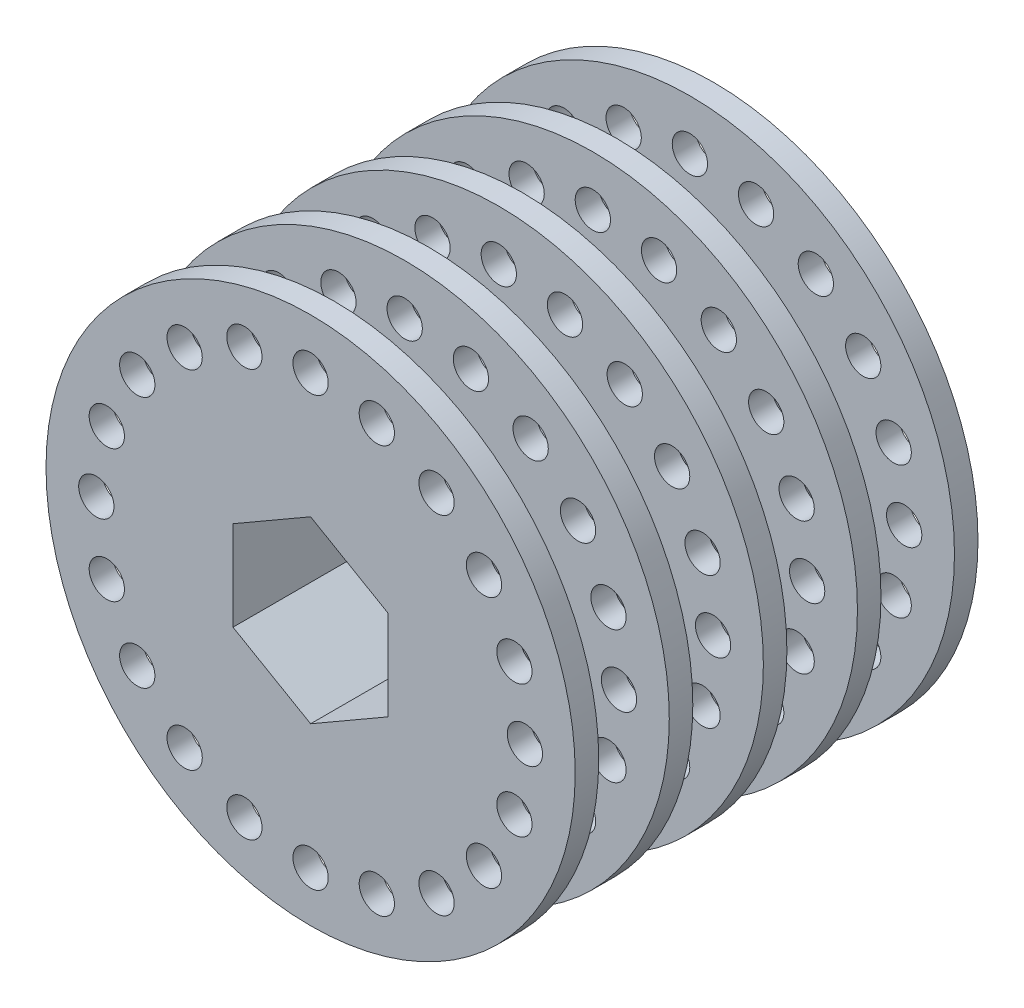
SolidWorks part; units mm, degrees
ref_plane "Front Plane" through (0, 0, 0) normal (0, 0, 1) x (1, 0, 0)
ref_plane "Top Plane" through (0, 0, 0) normal (0, 1, 0) x (1, 0, 0)
ref_plane "Right Plane" through (0, 0, 0) normal (1, 0, 0) x (0, 0, -1)
sketch "Sketch1" plane through (0, 0, 0) normal (0, 0, 1) x (1, 0, 0)
  circle A0 centre (0, 0) radius 10.16
  circle A1 centre (0, 0) radius 22.5
  circle A2 centre (0, 18.2218) radius 1.5
  circle A3 centre (5.6309, 17.33) radius 1.5
  circle A4 centre (10.7105, 14.7418) radius 1.5
  circle A5 centre (14.7418, 10.7105) radius 1.5
  circle A6 centre (17.33, 5.6309) radius 1.5
  circle A7 centre (18.2218, 0) radius 1.5
  circle A8 centre (17.33, -5.6309) radius 1.5
  circle A9 centre (14.7418, -10.7105) radius 1.5
  circle A10 centre (10.7105, -14.7418) radius 1.5
  circle A11 centre (5.6309, -17.33) radius 1.5
  circle A12 centre (0, -18.2218) radius 1.5
  circle A13 centre (-5.6309, -17.33) radius 1.5
  circle A14 centre (-10.7105, -14.7418) radius 1.5
  circle A15 centre (-14.7418, -10.7105) radius 1.5
  circle A16 centre (-17.33, -5.6309) radius 1.5
  circle A17 centre (-18.2218, 0) radius 1.5
  circle A18 centre (-17.33, 5.6309) radius 1.5
  circle A19 centre (-14.7418, 10.7105) radius 1.5
  circle A20 centre (-10.7105, 14.7418) radius 1.5
  circle A21 centre (-5.6309, 17.33) radius 1.5
  point P47 (0, 0)
  dimension "D1" = 20.32
  dimension "D2" = 45
  dimension "D3" = 3
  dimension "D4" = 20
extrude "Boss-Extrude1" add sketch "Sketch1" along normal blind 2 contours A0 | A1 A21 A20 A19 A18 A17 A16 A15 A14 A13 A12 A11 A10 A9 A8 A7 A6 A5 A4 A3 A2 A0 region at (0, 0, 0) region at (-21.8636, 0, 0)
extrude "Boss-Extrude2" add sketch "Sketch1<3>" against normal blind 6.25 contours A0 region at (0, 0, 0)
sketch "Sketch1<3>" plane through (0, 0, 0) normal (0, 0, 1) x (1, 0, 0) same geometry as "Sketch1"
pattern_linear "LPattern2" count 4 spacing 8 along (0, 0, -1) of "Boss-Extrude2", "Boss-Extrude1"
sketch "Sketch2" plane through (0, 0, -30.25) normal (0, 0, -1) x (-1, 0, 0)
  circle A1 centre (0, 0) radius 10.16 construction
  circle A2 centre (0, 0) radius 22.5 construction
  circle A3 centre (0, 0) radius 10.16
  circle A4 centre (0, 0) radius 22.5
  circle A5 centre (10.7105, 14.7418) radius 1.5
  circle A6 centre (10.7105, 14.7418) radius 1.5
  circle A7 centre (14.7418, 10.7105) radius 1.5
  circle A8 centre (14.7418, 10.7105) radius 1.5
  circle A9 centre (17.33, 5.6309) radius 1.5
  circle A10 centre (17.33, 5.6309) radius 1.5
  circle A11 centre (18.2218, 0) radius 1.5
  circle A12 centre (18.2218, 0) radius 1.5
  circle A13 centre (17.33, -5.6309) radius 1.5
  circle A14 centre (17.33, -5.6309) radius 1.5
  circle A15 centre (14.7418, -10.7105) radius 1.5
  circle A16 centre (14.7418, -10.7105) radius 1.5
  circle A17 centre (10.7105, -14.7418) radius 1.5
  circle A18 centre (10.7105, -14.7418) radius 1.5
  circle A19 centre (5.6309, -17.33) radius 1.5
  circle A20 centre (5.6309, -17.33) radius 1.5
  circle A21 centre (0, -18.2218) radius 1.5
  circle A22 centre (0, -18.2218) radius 1.5
  circle A23 centre (-5.6309, -17.33) radius 1.5
  circle A24 centre (-5.6309, -17.33) radius 1.5
  circle A25 centre (-10.7105, -14.7418) radius 1.5
  circle A26 centre (-10.7105, -14.7418) radius 1.5
  circle A27 centre (-14.7418, -10.7105) radius 1.5
  circle A28 centre (-14.7418, -10.7105) radius 1.5
  circle A29 centre (-17.33, -5.6309) radius 1.5
  circle A30 centre (-17.33, -5.6309) radius 1.5
  circle A31 centre (-18.2218, 0) radius 1.5
  circle A32 centre (-18.2218, 0) radius 1.5
  circle A33 centre (-17.33, 5.6309) radius 1.5
  circle A34 centre (-17.33, 5.6309) radius 1.5
  circle A35 centre (-14.7418, 10.7105) radius 1.5
  circle A36 centre (-14.7418, 10.7105) radius 1.5
  circle A37 centre (-10.7105, 14.7418) radius 1.5
  circle A38 centre (-10.7105, 14.7418) radius 1.5
  circle A39 centre (-5.6309, 17.33) radius 1.5
  circle A40 centre (-5.6309, 17.33) radius 1.5
  circle A41 centre (0, 18.2218) radius 1.5
  circle A42 centre (0, 18.2218) radius 1.5
  circle A43 centre (0, 0) radius 10.16
  circle A44 centre (0, 0) radius 10.16
  circle A45 centre (5.6309, 17.33) radius 1.5
  circle A46 centre (5.6309, 17.33) radius 1.5
  circle M22 centre (0, 0) radius 10.16
  dimension "D1" = 0
  dimension "D2" = 0
  dimension "D3" = 0
  dimension "D4" = 0
  dimension "D5" = 0
  dimension "D6" = 0
  dimension "D7" = 0
  dimension "D8" = 0
  dimension "D9" = 0
  dimension "D10" = 0
  dimension "D11" = 0
  dimension "D12" = 0
  dimension "D13" = 0
  dimension "D14" = 0
  dimension "D15" = 0
  dimension "D16" = 0
  dimension "D17" = 0
  dimension "D18" = 0
  dimension "D19" = 0
  dimension "D20" = 0
  dimension "D21" = 0
extrude "Boss-Extrude3" add sketch "Sketch2" along normal blind 2 contours A4 A46 A42 A40 A38 A36 A34 A32 A30 A28 A26 A24 A22 A20 A18 A16 A14 A12 A10 A8 A6 M22 | M22 region at (0, 0, -30.25) region at (21.8636, 0, -30.25)
sketch "Sketch3" plane through (0, 0, -32.25) normal (0, 0, -1) x (-1, 0, 0)
  line L1 (0, 7.621) -> (-6.6, 3.8105)
  line L2 (-6.6, 3.8105) -> (-6.6, -3.8105)
  line L3 (-6.6, -3.8105) -> (0, -7.621)
  line L4 (0, -7.621) -> (6.6, -3.8105)
  line L5 (6.6, -3.8105) -> (6.6, 3.8105)
  line L6 (6.6, 3.8105) -> (0, 7.621)
  circle A0 centre (0, 0) radius 6.6 construction
  circle A2 centre (0, 0) radius 19.05
  dimension "D2" = 38.1
extrude "Cut-Extrude1" cut sketch "Sketch3" against normal through all contours L5 L6 L1 L2 L3 L4 region at (0, 0, -32.25)
ref_plane "Plane1" through (0, 0, -3) normal (0, 0, -1) x (-1, 0, 0)
ref_plane "Plane2" through (0, 0, -11) normal (0, 0, -1) x (-1, 0, 0)
sketch "Sketch4" plane through (0, 0, -32.25) normal (0, 0, -1) x (-1, 0, 0)
  line L0 (-6.6, -3.8105) -> (0, -7.621) construction
  line L1 (0, -7.621) -> (6.6, -3.8105) construction
  line L2 (6.6, -3.8105) -> (6.6, 3.8105) construction
  line L3 (6.6, 3.8105) -> (0, 7.621) construction
  line L4 (6.6, -3.8105) -> (0, -7.621) construction
  line L5 (-6.6, 3.8105) -> (-6.6, -3.8105) construction
  line L6 (-6.6, -3.8105) -> (0, -7.621)
  line L7 (0, -7.621) -> (6.6, -3.8105)
  line L8 (6.6, -3.8105) -> (6.6, 3.8105)
  line L9 (6.6, 3.8105) -> (0, 7.621)
  line L10 (6.6, -3.8105) -> (0, -7.621)
  line L11 (-6.6, 3.8105) -> (-6.6, -3.8105)
  circle A0 centre (0, 0) radius 10.16 construction
  circle A1 centre (0, 0) radius 10.16
  line M1 (6.6, 3.8105) -> (6.6, -3.8105)
  line M2 (6.6, -3.8105) -> (0, -7.621)
  line M3 (0, -7.621) -> (-6.6, -3.8105)
  line M4 (-6.6, -3.8105) -> (-6.6, 3.8105)
  line M5 (-6.6, 3.8105) -> (0, 7.621)
  line M6 (0, 7.621) -> (6.6, 3.8105)
extrude "Boss-Extrude5" add sketch "Sketch4" against normal up to surface (34.25 mm away) contours A1 M6 M1 M2 M3 M4 M5 region at (9.8726, 0, -32.25) up to face at (0, 0, 2)
chamfer "Chamfer1" distance 1 angle 45 8 edges at (10.16, 0, -30.25) (10.16, 0, -24) (10.16, 0, -22) (10.16, 0, -16) (10.16, 0, -14) (10.16, 0, -8) (10.16, 0, -6) (10.16, 0, 0)
